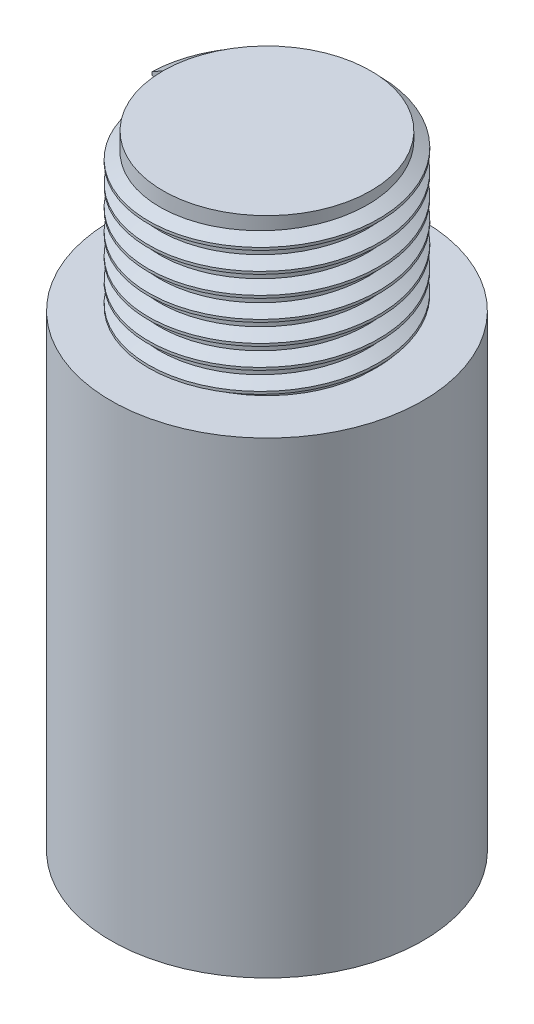
SolidWorks part; units mm, degrees
ref_plane "Front Plane" through (0, 0, 0) normal (0, 0, 1) x (1, 0, 0)
ref_plane "Top Plane" through (0, 0, 0) normal (0, 1, 0) x (1, 0, 0)
ref_plane "Right Plane" through (0, 0, 0) normal (1, 0, 0) x (0, 0, -1)
sketch "Sketch1" plane through (0, 0, 0) normal (0, 0, 1) x (1, 0, 0)
  line L0 (0, 0) -> (0, 38.1) construction
  line L1 (0, 0) -> (9.525, 0)
  line L2 (9.525, 0) -> (9.525, 28.575)
  line L3 (9.525, 28.575) -> (6.35, 28.575)
  line L4 (6.35, 28.575) -> (6.35, 38.1)
  line L5 (6.35, 38.1) -> (0, 38.1)
  line L6 (0, 0) -> (0, 38.1)
  dimension "D1" = 38.1
  dimension "D2" = 9.525
  dimension "D3" = 6.35
  dimension "D4" = 9.525
revolve "Revolve1" add sketch "Sketch1" angle 360 about L0
thread "Thread1" pitch 1.27 method extrude profile "Thread Profile2" start angle 0, offset 0, length 10, pitch 1.27, diameter 12.7
ref_plane "Plane2" through (-6.35, 38.1, 0) normal (0, 0, 1) x (-1, 0, 0)
sketch "Thread Profile2" plane through (-6.35, 38.1, 0) normal (0, 0, 1) x (-1, 0, 0)
  line L0 (0, 0) -> (0, 1.27) construction
  line L1 (0, 0) -> (0.6874, 0.3969)
  line L2 (0.6874, 0.3969) -> (0.6874, 0.5556)
  line L3 (0.6874, 0.5556) -> (0, 0.9525)
  line L4 (0.6874, 0.4762) -> (0, 0.4762) construction
  line L11 (0, 0) -> (0, 0.9525)
  point P2 (0, 0)
  dimension "Pitch" = 1.27
  dimension "Profile_Angle" = 60
  dimension "Profile_Land" = 0.1588
  dimension "Profile_Height" = 0.6874
